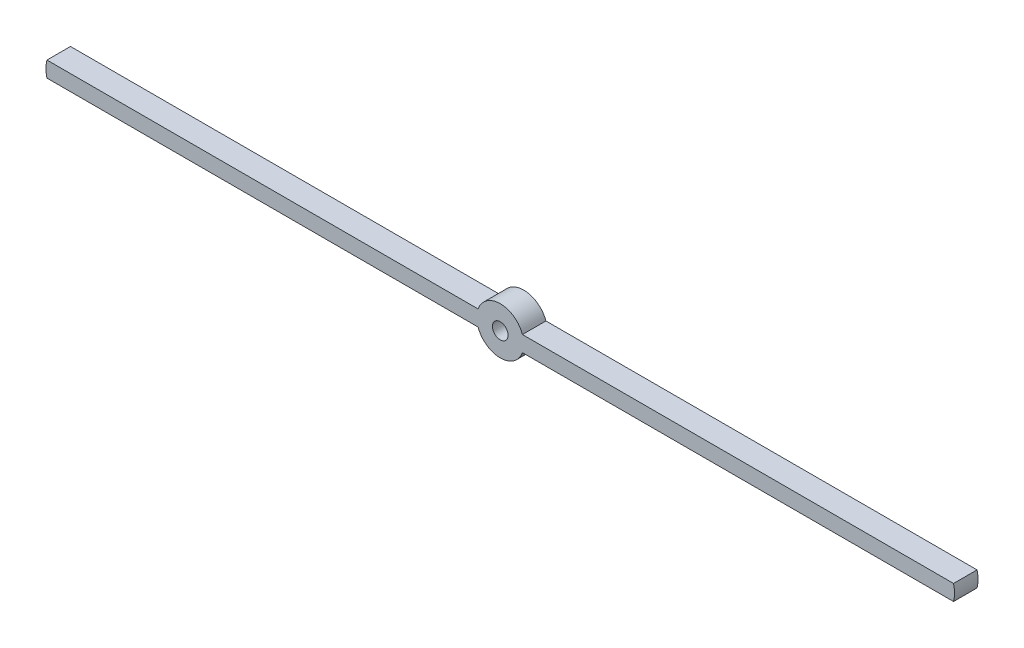
SolidWorks part; units mm, degrees
ref_plane "Plan de face" through (0, 0, 0) normal (0, 0, 1) x (1, 0, 0)
ref_plane "Plan de dessus" through (0, 0, 0) normal (0, 1, 0) x (1, 0, 0)
ref_plane "Plan de droite" through (0, 0, 0) normal (1, 0, 0) x (0, 0, -1)
sketch "Esquisse1" plane through (0, 0, 0) normal (0, 0, 1) x (1, 0, 0)
  line L1 (-5.6569, 2) -> (-115.6569, 2)
  line L2 (-5.6569, 2) -> (-5.6569, -2) construction
  line L3 (-5.6569, -2) -> (-115.6569, -2)
  line L4 (-115.6569, 2) -> (-115.6569, -2) construction
  line L5 (5.6569, 2) -> (115.6569, 2)
  line L6 (5.6569, 2) -> (5.6569, -2) construction
  line L7 (5.6569, -2) -> (115.6569, -2)
  line L8 (115.6569, 2) -> (115.6569, -2) construction
  circle A0 centre (0, 0) radius 2
  circle A1 centre (0, 0) radius 6 construction
  arc A2 (-115.6569, 2) -> (-115.6569, -2) centre (-107.9109, 0) ccw
  arc A3 (115.6569, 2) -> (115.6569, -2) centre (107.9109, 0) cw
  arc A4 (-5.6569, 2) -> (5.6569, 2) centre (0, 0) cw
  arc A5 (5.6569, -2) -> (-5.6569, -2) centre (0, 0) cw
  dimension "D1" = 4
  dimension "D5" = 8
  dimension "D2" = 4
  dimension "D3" = 4
  dimension "D4" = 110
extrude "Boss.-Extru.1" add sketch "Esquisse1" along normal blind 6 contours A0 | L3 A2 L1 A4 L5 A3 L7 A5 region at (0, 0, 0)
